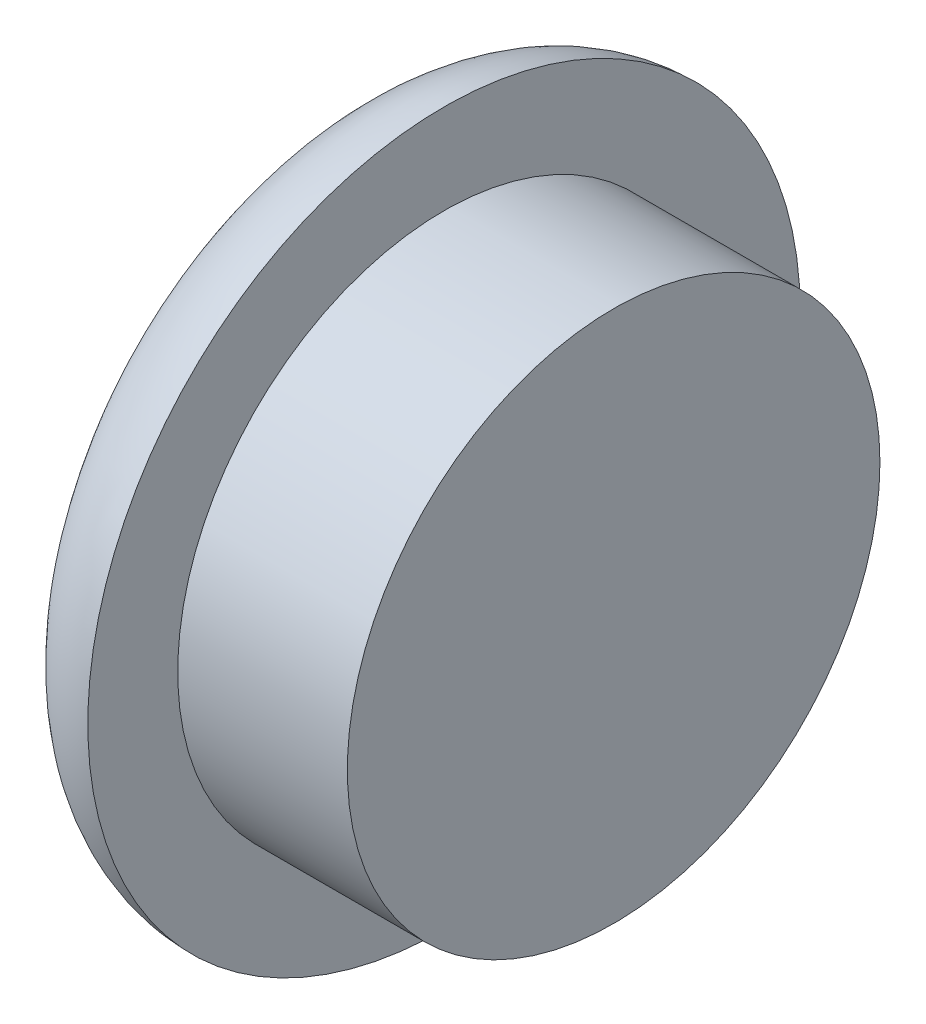
SolidWorks part; units mm, degrees
ref_plane "Front Plane" through (0, 0, 0) normal (0, 0, 1) x (1, 0, 0)
ref_plane "Top Plane" through (0, 0, 0) normal (0, 1, 0) x (1, 0, 0)
ref_plane "Right Plane" through (0, 0, 0) normal (1, 0, 0) x (0, 0, -1)
sketch "Sketch1" plane through (0, 0, 0) normal (1, 0, 0) x (0, 0, -1)
  circle A0 centre (0, 0) radius 7.85
  circle A1 centre (0, 0) radius 10.5
  dimension "D1" = 15.7
  dimension "D2" = 21
extrude "Boss-Extrude1" add sketch "Sketch1" along normal blind 5 contours A0
extrude "Boss-Extrude2" add sketch "Sketch1<3>" against normal blind 3 contours A1
sketch "Sketch1<3>" plane through (0, 0, 0) normal (1, 0, 0) x (0, 0, -1) same geometry as "Sketch1"
fillet "Fillet1" radius 3 1 edges at (-3, 0, -10.5)
